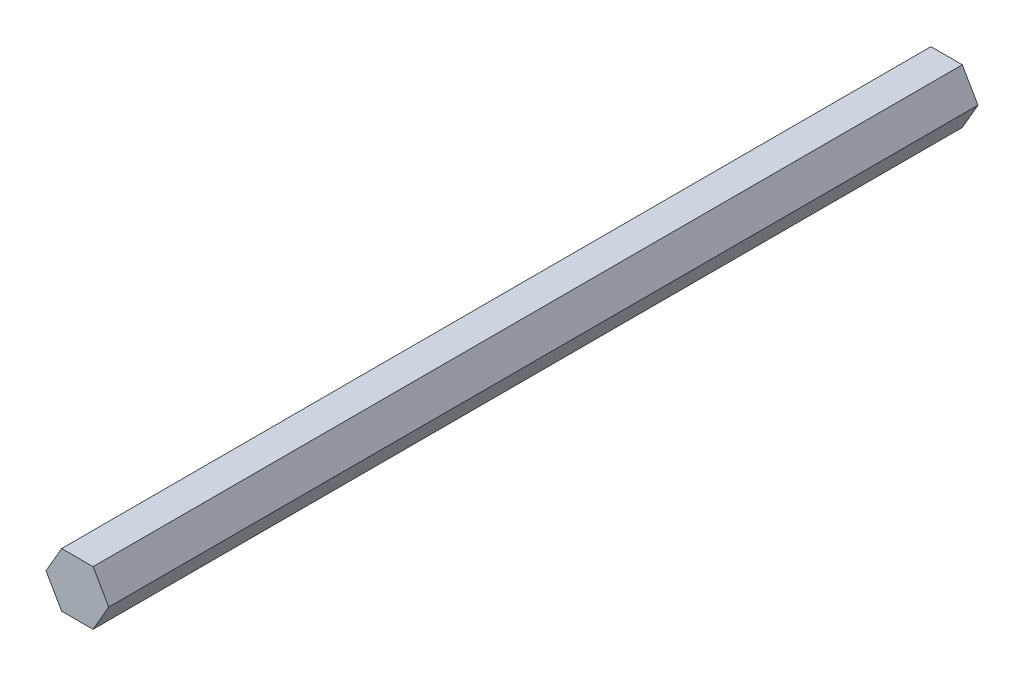
SolidWorks part; units mm, degrees
ref_plane "Front Plane" through (0, 0, 0) normal (0, 0, 1) x (1, 0, 0)
ref_plane "Top Plane" through (0, 0, 0) normal (0, 1, 0) x (1, 0, 0)
ref_plane "Right Plane" through (0, 0, 0) normal (1, 0, 0) x (0, 0, -1)
sketch "Sketch1" plane through (0, 0, 0) normal (0, 0, 1) x (1, 0, 0)
  line L1 (3.6635, -6.3515) -> (7.3323, -0.003)
  line L2 (7.3323, -0.003) -> (3.6688, 6.3485)
  line L3 (3.6688, 6.3485) -> (-3.6635, 6.3515)
  line L4 (-3.6635, 6.3515) -> (-7.3323, 0.003)
  line L5 (-7.3323, 0.003) -> (-3.6688, -6.3485)
  line L6 (-3.6688, -6.3485) -> (3.6635, -6.3515)
  circle A0 centre (0, 0) radius 6.35 construction
  dimension "D1" = 12.7
extrude "Boss-Extrude1" add sketch "Sketch1" along normal blind 203.2
sketch "Sketch2" plane through (0, 0, 0) normal (0, 0, -1) x (-1, 0, 0)
  circle A0 centre (0, 0) radius 6.35
